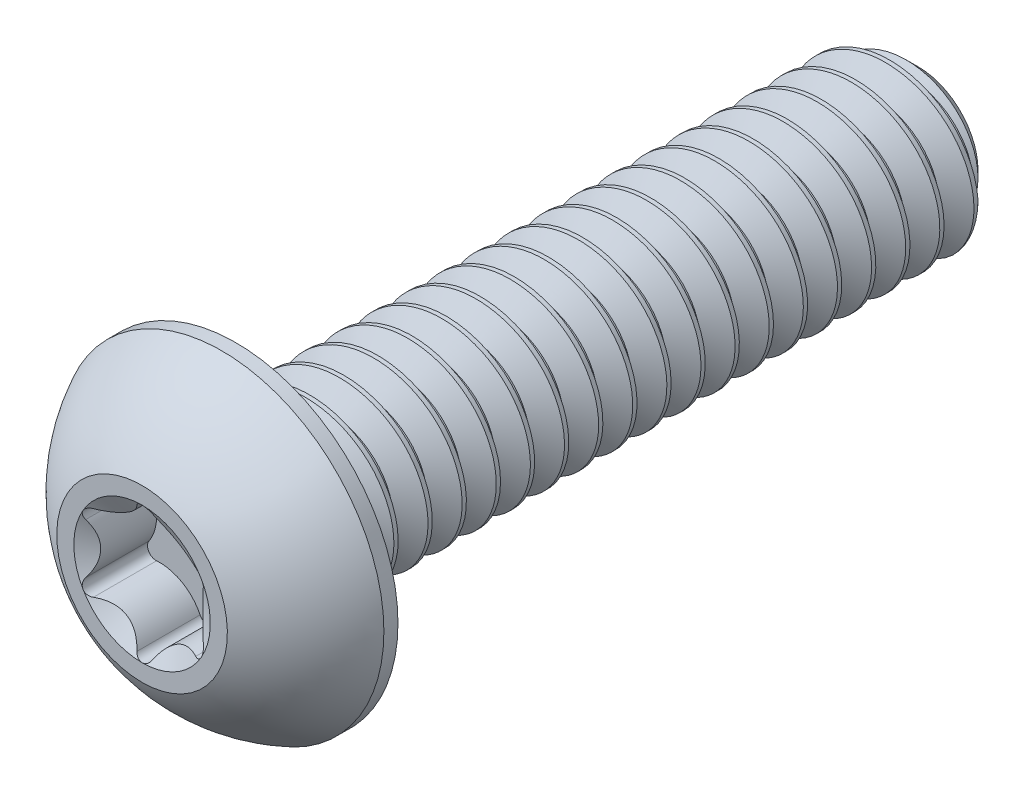
SolidWorks part; units mm, degrees
ref_plane "Front" through (0, 0, 0) normal (0, 0, 1) x (1, 0, 0)
ref_plane "Top" through (0, 0, 0) normal (0, 1, 0) x (1, 0, 0)
ref_plane "Right" through (0, 0, 0) normal (1, 0, 0) x (0, 0, -1)
sketch "Sketch1" plane through (0, 0, 0) normal (1, 0, 0) x (0, 0, -1)
  line L2 (1.1, 1) -> (9.1, 1)
  line L3 (9.1, 1) -> (9.1, 0)
  line L4 (9.1, 0) -> (1.1, 0)
  line L6 (0.935, 1.9) -> (1.1, 1.9) construction
  line L7 (9.1, 1) -> (9.1, -1) construction
  line L8 (0, 0) -> (1.1, 0) construction
  line L9 (1.1, 1.9) -> (1.1, -1.9) construction
  line L11 (1.1, 1) -> (1.1, 0)
  line L14 (0, 0) -> (0, 1) construction
  arc A3 (0, 1) -> (0.935, 1.9) centre (1.8632, 0) cw construction
  dimension "D1" = 0.165
  dimension "Head Ht" = 1.1
  dimension "Head Dia" = 3.8
  dimension "Dia" = 2
  dimension "Lg" = 8
revolve "Revolve1" add sketch "Sketch1" angle 360 mid plane about L4
sketch "Sketch3" plane through (0, 0, -9.1) normal (0, 0, -1) x (-1, 0, 0)
  circle A0 centre (0, 0) radius 1
curve "Helix/Spiral1" pitch 0.4 height 8.4 radius 1 centre (0, 0, -9.1) axis (0, 0, 1) start towards (0, 1, 0)
sketch "Sketch2" plane through (0, 0, 0) normal (1, 0, 0) x (0, 0, -1)
  line L0 (9.1, 1) -> (9.45, 1)
  line L1 (9.45, 1) -> (9.3, 0.7402)
  line L2 (9.3, 0.7402) -> (9.25, 0.7402)
  line L3 (9.25, 0.7402) -> (9.1, 1)
  line L4 (9.175, 0.8701) -> (9.375, 0.8701) construction
  dimension "D1" = 60
  dimension "D2" = 0.05
  dimension "D3" = 0.2
chamfer "Chamfer1" distance 0.3 angle 45 1 edges at (0, 1, -9.1)
sweep "Cut-Sweep1" cut profiles "Sketch2" path "Helix/Spiral1" align with end faces yes
sketch "Sketch7" plane through (0, 0, 0) normal (1, 0, 0) x (0, 0, -1)
  line L0 (0, 0) -> (0, 1) construction
  line L6 (0.935, 1.9) -> (1.1, 1.9) construction
  line L8 (0, 0) -> (1.1, 0) construction
  line L11 (1.1, 1.9) -> (1.1, -1.9) construction
  line L12 (0.935, 1.9) -> (1.1, 1.9)
  line L13 (0, 0) -> (1.1, 0)
  line L15 (1.1, 1.9) -> (1.1, 0)
  line L16 (0, 1) -> (0, 0)
  arc A2 (0.935, 1.9) -> (0, 1) centre (1.8632, 0) ccw construction
  arc A3 (0.935, 1.9) -> (0, 1) centre (1.8632, 0) ccw
revolve "Revolve2" add sketch "Sketch7" angle 360 mid plane about L13
sketch "Sketch5" plane through (0, 0, 0) normal (0, 0, 1) x (1, 0, 0)
  line L0 (2.6125, 0) -> (-2.6125, 0) construction
  line L2 (0, 0) -> (-0.6928, 0.4)
  line L3 (0, 0) -> (-0.6928, -0.4)
  line L4 (0, 0.8) -> (0, 0.7) construction
  line L5 (0, 0.7) -> (0, 0.6) construction
  circle A0 centre (0, 0) radius 0.6 construction
  circle A1 centre (0, 0) radius 0.7 construction
  circle A2 centre (0, 0) radius 0.8 construction
  arc A3 (-0.6894, 0.2944) -> (-0.6894, -0.2944) centre (-1.1298, 0) cw
  arc A4 (-0.6894, 0.2944) -> (-0.6928, 0.4) centre (-0.6062, 0.35) cw
  arc A5 (-0.6894, -0.2944) -> (-0.6928, -0.4) centre (-0.6062, -0.35) ccw
  dimension "D2" = 1.6
  dimension "D4" = 1.2
  dimension "D1" = 30
extrude "Cut-Extrude2" cut sketch "Sketch5" against normal blind 0.77
pattern_circular "CirPattern1" count 6 over 360 of "Cut-Extrude2"
sketch "Sketch11" plane through (0, 0, 0) normal (0, 0, 1) x (1, 0, 0)
  circle A0 centre (0, 0) radius 0.8 construction
  circle A1 centre (0, 0) radius 0.8
extrude "Cut-Extrude3" cut sketch "Sketch11" against normal blind 0.77 draft 60
sketch "Sketch9" [suppressed] plane through (0, 0, -1.4986) normal (0, 0, 1) x (1, 0, 0)
  circle A2 centre (0, 0) radius 1.4224
extrude "Boss-Extrude2" [suppressed] add sketch "Sketch9" against normal offset from surface (7.0104 mm away) 31.75 up to face at (0, 0.7, -9.1)
sketch "Sketch10" plane through (0, 0, 0) normal (1, 0, 0) x (0, 0, -1)
  line L0 (9.1, 1) -> (9.1, -1) construction
  point P0 (8.5, -1)
  dimension "D1" = 0.6
equation "\"D3@Helix/Spiral1\" = \"Lg@Sketch1\" + \"D4@Helix/Spiral1\""
equation "\"D2@Sketch2\" = \"D4@Helix/Spiral1\" * .125"
equation "\"D3@Sketch2\" = \"D4@Helix/Spiral1\" * .5"
equation "\"D1@Chamfer1\" = \"D4@Helix/Spiral1\" * .75"
equation "\"D1@Cut-Extrude2\" = \"Head Ht@Sketch1\" * .7"
equation "\"D1@Sketch1\" = \"Head Ht@Sketch1\" * .15"
equation "\"D1@Sketch10\" = \"D4@Helix/Spiral1\" * 1.5"
equation "\"D1@Cut-Extrude3\" = \"D1@Cut-Extrude2\""
equation "\"D2@Sketch5\" = \"Dia@Sketch1\" * .8"
equation "\"D4@Sketch5\" = \"D2@Sketch5\" * .75"
